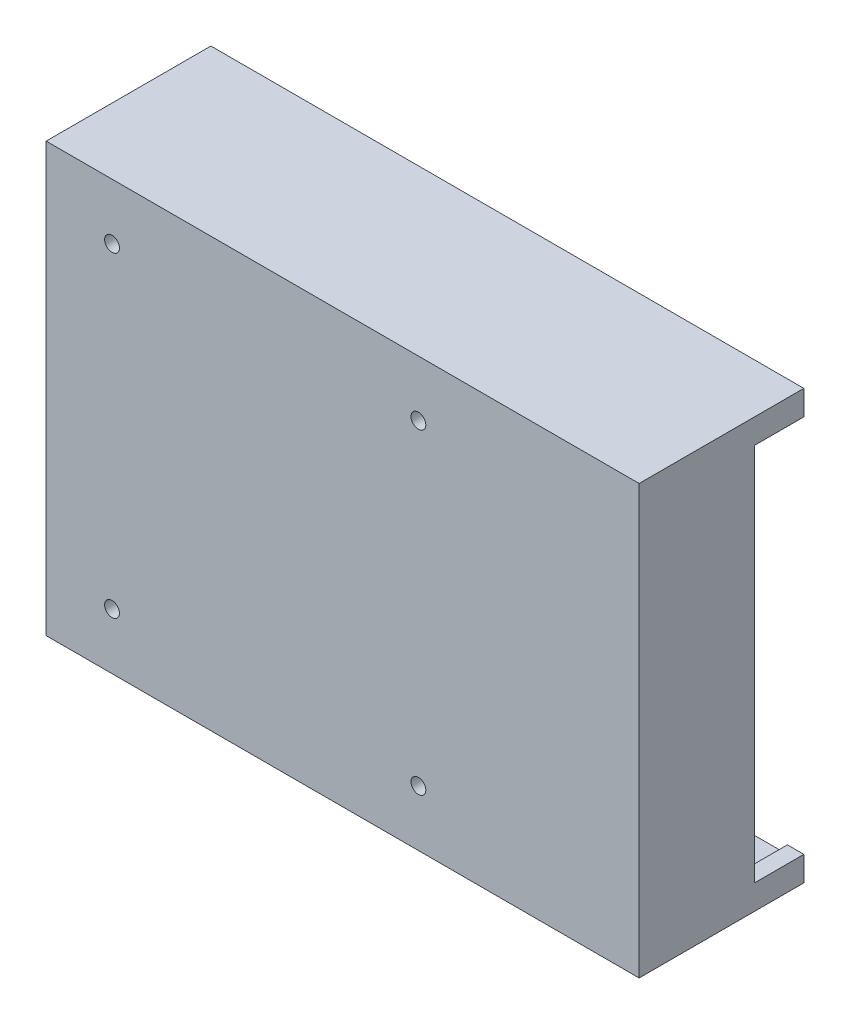
SolidWorks part; units mm, degrees
ref_plane "Front Plane" through (0, 0, 0) normal (0, 0, 1) x (1, 0, 0)
ref_plane "Top Plane" through (0, 0, 0) normal (0, 1, 0) x (1, 0, 0)
ref_plane "Right Plane" through (0, 0, 0) normal (1, 0, 0) x (0, 0, -1)
sketch "Sketch1" plane through (0, 0, 0) normal (0, 0, 1) x (1, 0, 0)
  line L1 (90, -65) -> (-90, -65)
  line L2 (90, -65) -> (90, 65)
  line L3 (90, 65) -> (-90, 65)
  line L4 (-90, -65) -> (-90, 65)
  line L5 (90, -65) -> (-90, 65) construction
  line L6 (90, 65) -> (-90, -65) construction
  point P0 (0, 0)
  point P6 (23, 48)
  point P7 (-70, 48)
  point P8 (-70, -48)
  point P9 (23, -48)
  point P10 (0, 0)
  point P11 (0, 0)
  point P12 (0, 0)
  point P13 (0, 0)
  point P14 (0, 0)
  point P15 (0, 0)
  dimension "D1" = 130
  dimension "D2" = 180
  dimension "D3" = 96
  dimension "D4" = 93
  dimension "D5" = 20
  dimension "D6" = 17
extrude "Boss-Extrude1" add sketch "Sketch1" along normal blind 50
sketch "Sketch3" plane through (0, 0, 0) normal (0, 0, 1) x (1, 0, 0)
  line L0 (90, -65) -> (90, 65) construction
  line L1 (-85, -60) -> (85, -60)
  line L2 (-85, -60) -> (-85, 60)
  line L3 (-85, 60) -> (85, 60)
  line L4 (85, -60) -> (85, 60)
  line L5 (-85, -60) -> (85, 60) construction
  line L6 (-85, 60) -> (85, -60) construction
  line L8 (90, 65) -> (-90, 65) construction
  point P0 (0, 0)
  dimension "D1" = 5
  dimension "D2" = 5
extrude "Cut-Extrude1" cut sketch "Sketch3" along normal blind 45
hole_wizard "M4 Clearance Hole1" positions "Sketch4" profile "Sketch5" hole size "M4" standard "ANSI Metric" end condition through all
sketch "Sketch4" plane through (0, 0, 45) normal (0, 0, -1) x (-1, 0, 0)
  point P0 (-23, -48)
  point P3 (70, -48)
  point P6 (70, 48)
  point P9 (-23, 48)
sketch "Sketch5" plane through (23, -48, 45) normal (1, 0, 0) x (0, 1, 0)
  line L0 (0, 0) -> (0, 5)
  line L1 (0, 5) -> (2.25, 5)
  line L2 (2.25, 5) -> (2.25, 0)
  line L5 (2.25, 0) -> (0, 0)
  line L11 (0, -6.35) -> (0, 107.95) construction
  dimension "Thru Hole Dia." = 4.5
  dimension "Thru Hole Depth" = 5
sketch "Sketch7" plane through (90, 0, 0) normal (1, 0, 0) x (0, 0, -1)
  line L0 (0, -65) -> (0, 65) construction
  line L1 (0, 57.5) -> (-15, 57.5)
  line L2 (0, 57.5) -> (0, -57.5)
  line L3 (0, -57.5) -> (-15, -57.5)
  line L4 (-15, 57.5) -> (-15, -57.5)
  point P6 (0, 0)
  dimension "D1" = 15
  dimension "D2" = 115
extrude "Cut-Extrude2" cut sketch "Sketch7" against normal up to surface (180 mm away) up to face at (-90, 0, 25)
